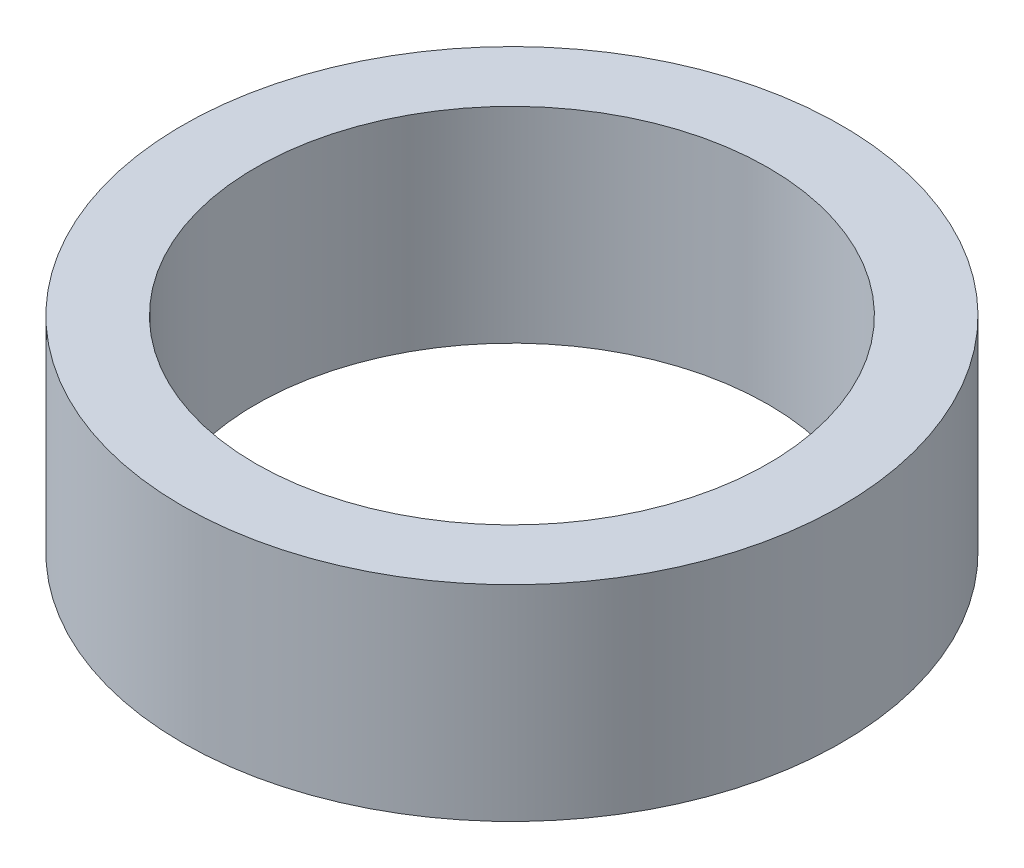
SolidWorks part; units mm, degrees
ref_plane "Front Plane" through (0, 0, 0) normal (0, 0, 1) x (1, 0, 0)
ref_plane "Top Plane" through (0, 0, 0) normal (0, 1, 0) x (1, 0, 0)
ref_plane "Right Plane" through (0, 0, 0) normal (1, 0, 0) x (0, 0, -1)
sketch "Sketch1" plane through (0, 0, 0) normal (0, 1, 0) x (1, 0, 0)
  circle A0 centre (0, 0) radius 45
  dimension "FLANGE_OD" = 90
extrude "Boss-Extrude1" add sketch "Sketch1" along normal blind 28
sketch "Sketch2" plane through (0, 0, 0) normal (0, 1, 0) x (1, 0, 0)
  circle A0 centre (0, 0) radius 35
  dimension "BORE_D" = 70
extrude "Cut-Extrude1" cut sketch "Sketch2" along normal through all
sketch "Sketch3" plane through (0, 28, 0) normal (0, 1, 0) x (1, 0, 0)
  circle A0 centre (0, 0) radius 19.3484 construction
  circle A1 centre (-19.3484, 0) radius 1.7045
  dimension "BOLT_D" = 3.409
  dimension "BOLT_PCD" = 38.6969
extrude "Cut-Extrude2" cut sketch "Sketch3" against normal blind 17.568 rebuild error yes
pattern_circular "CirPattern1" count 8 over 360 rebuild error yes
